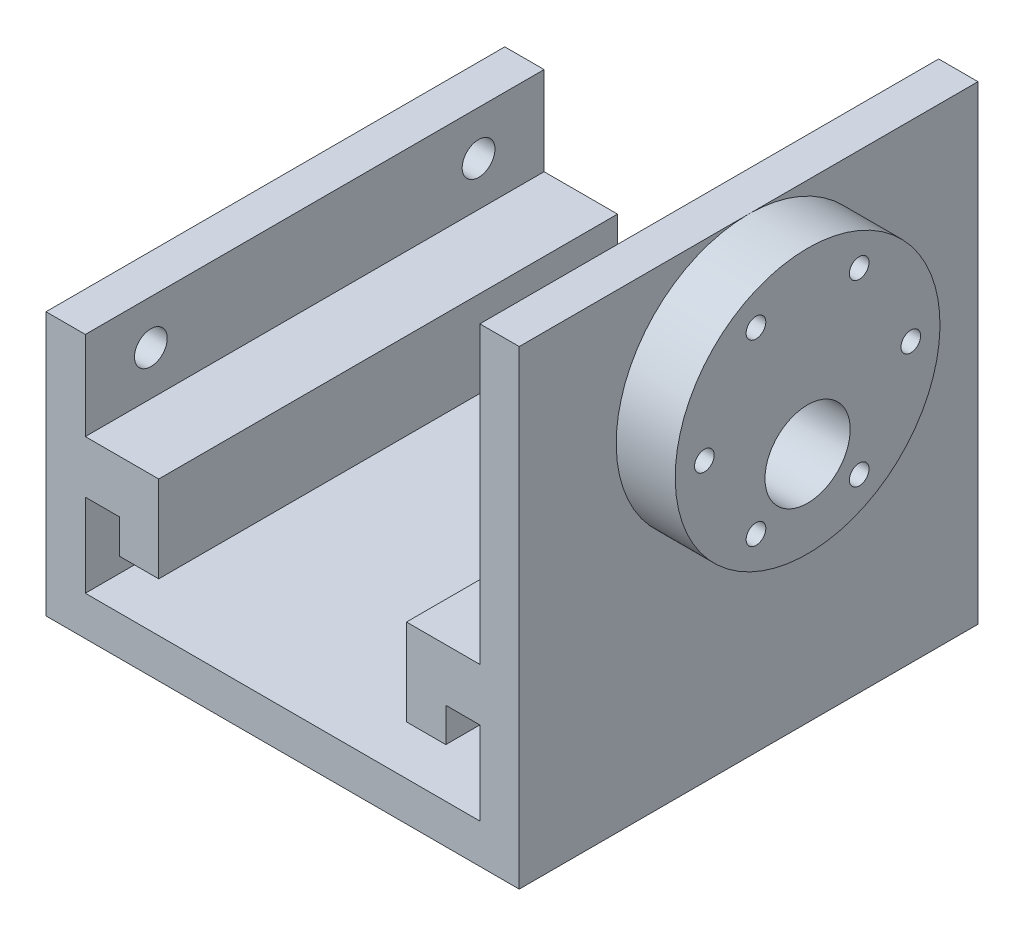
SolidWorks part; units mm, degrees
material "Nylon 101"
ref_plane "Front Plane" through (0, 0, 0) normal (0, 0, 1) x (1, 0, 0)
ref_plane "Top Plane" through (0, 0, 0) normal (0, 1, 0) x (1, 0, 0)
ref_plane "Right Plane" through (0, 0, 0) normal (1, 0, 0) x (0, 0, -1)
sketch "Sketch1" plane through (0, 0, 0) normal (0, 0, 1) x (1, 0, 0)
  line L0 (0, 26.7) -> (0, 0)
  line L1 (0, 0) -> (72.2, 0)
  line L2 (72.2, 0) -> (72.2, 71.7)
  line L3 (72.2, 71.7) -> (66.2, 71.7)
  line L4 (66.2, 71.7) -> (66.2, 26.7)
  line L5 (66.2, 6) -> (6, 6)
  line L6 (6, 6) -> (6, 18.7)
  line L7 (6, 18.7) -> (11.2, 18.7)
  line L8 (0, 26.7) -> (17.2, 26.7)
  line L10 (11.2, 18.7) -> (11.2, 13.5)
  line L11 (11.2, 13.5) -> (17.2, 13.5)
  line L12 (17.2, 13.5) -> (17.2, 26.7)
  line L13 (66.2, 26.7) -> (55, 26.7)
  line L14 (55, 26.7) -> (55, 13.5)
  line L15 (55, 13.5) -> (61, 13.5)
  line L16 (61, 13.5) -> (61, 18.7)
  line L17 (61, 18.7) -> (66.2, 18.7)
  line L18 (66.2, 18.7) -> (66.2, 6)
  dimension "D1" = 8
  dimension "D2" = 6
  dimension "D3" = 6
  dimension "D4" = 5.2
  dimension "D5" = 12.7
  dimension "D6" = 6
  dimension "D7" = 5.2
  dimension "D8" = 5.2
  dimension "D9" = 6
  dimension "D10" = 60.2
  dimension "D11" = 6
  dimension "D12" = 45
extrude "Boss-Extrude1" add sketch "Sketch1" along normal blind 70
sketch "Sketch2" plane through (66.2, 0, 0) normal (-1, 0, 0) x (0, 0, 1)
  circle A0 centre (35, 51.5) radius 15.75 construction
  circle A1 centre (50.75, 51.5) radius 1.5
  dimension "D3" = 31.5
  dimension "D2" = 51.5
  dimension "D4" = 3
  dimension "D1" = 35
extrude "Cut-Extrude1" cut sketch "Sketch2" against normal blind 6
sketch "Sketch3" plane through (0, 18.7, 0) normal (0, -1, 0) x (1, 0, 0)
  line L0 (61.1, 56) -> (66.1, 56)
  line L2 (0, 70) -> (72.2, 70) construction
  line L4 (61, 70) -> (61, 0) construction
  arc A0 (66.1, 56) -> (61.1, 56) centre (63.6, 56) ccw
  dimension "D1" = 5
  dimension "D2" = 14
  dimension "D3" = 2.6
revolve "Cut-Revolve1" cut sketch "Sketch3" angle 360 about L0
pattern_linear "LPattern1" count 4 spacing 14 along (0, 0, -1) count 2 spacing 55 along (-1, 0, 0) of "Cut-Revolve1"
ref_plane "Plane1" through (36.1, 0, 0) normal (-1, 0, 0) x (0, 0, 1)
ref_axis "Axis1" through (66.2, 51.5, 35) along (-1, 0, 0)
pattern_circular "CirPattern2" count 6 over 360 about axis through (66.2, 51.5, 35) along (-1, 0, 0) of "Cut-Extrude1"
sketch "Sketch10" plane through (66.2, 0, 0) normal (-1, 0, 0) x (0, 0, 1)
  circle A0 centre (35, 44.5) radius 6.5
  dimension "D1" = 13
  dimension "D2" = 7
extrude "Cut-Extrude4" cut sketch "Sketch10" against normal blind 10
sketch "Sketch11" plane through (72.2, 0, 0) normal (1, 0, 0) x (0, 0, -1)
  line L0 (-70, 71.7) -> (0, 71.7) construction
  circle A0 centre (-35, 51.5) radius 20.2
  circle A1 centre (-42.875, 65.1399) radius 1.5 construction
  circle A2 centre (-27.125, 65.1399) radius 1.5 construction
  circle A3 centre (-19.25, 51.5) radius 1.5 construction
  circle A4 centre (-27.125, 37.8601) radius 1.5 construction
  circle A5 centre (-35, 44.5) radius 6.5 construction
  circle A6 centre (-42.875, 37.8601) radius 1.5 construction
  circle A7 centre (-50.75, 51.5) radius 1.5 construction
  circle A8 centre (-42.875, 65.1399) radius 1.5
  circle A9 centre (-27.125, 65.1399) radius 1.5
  circle A10 centre (-19.25, 51.5) radius 1.5
  circle A11 centre (-27.125, 37.8601) radius 1.5
  circle A12 centre (-35, 44.5) radius 6.5
  circle A13 centre (-42.875, 37.8601) radius 1.5
  circle A14 centre (-50.75, 51.5) radius 1.5
extrude "Boss-Extrude6" add sketch "Sketch11" along normal blind 9
sketch "Sketch12" plane through (0, 0, 70) normal (1, 0, 0) x (0, 0, -1)
  line L1 (70, 26.7) -> (70, 0) construction
  line L2 (0, 26.7) -> (70, 26.7)
  line L3 (0, 26.7) -> (0, 40.2)
  line L4 (0, 40.2) -> (70, 40.2)
  line L5 (70, 26.7) -> (70, 40.2)
  circle A0 centre (10, 33.45) radius 2.5
  circle A1 centre (60, 33.45) radius 2.5
  dimension "D5" = 5
  dimension "D1" = 13.5
  dimension "D2" = 50
  dimension "D3" = 6.75
  dimension "D4" = 10
extrude "Boss-Extrude7" add sketch "Sketch12" along normal up to surface (6 mm away) up to face at (6, 12.35, 35)
